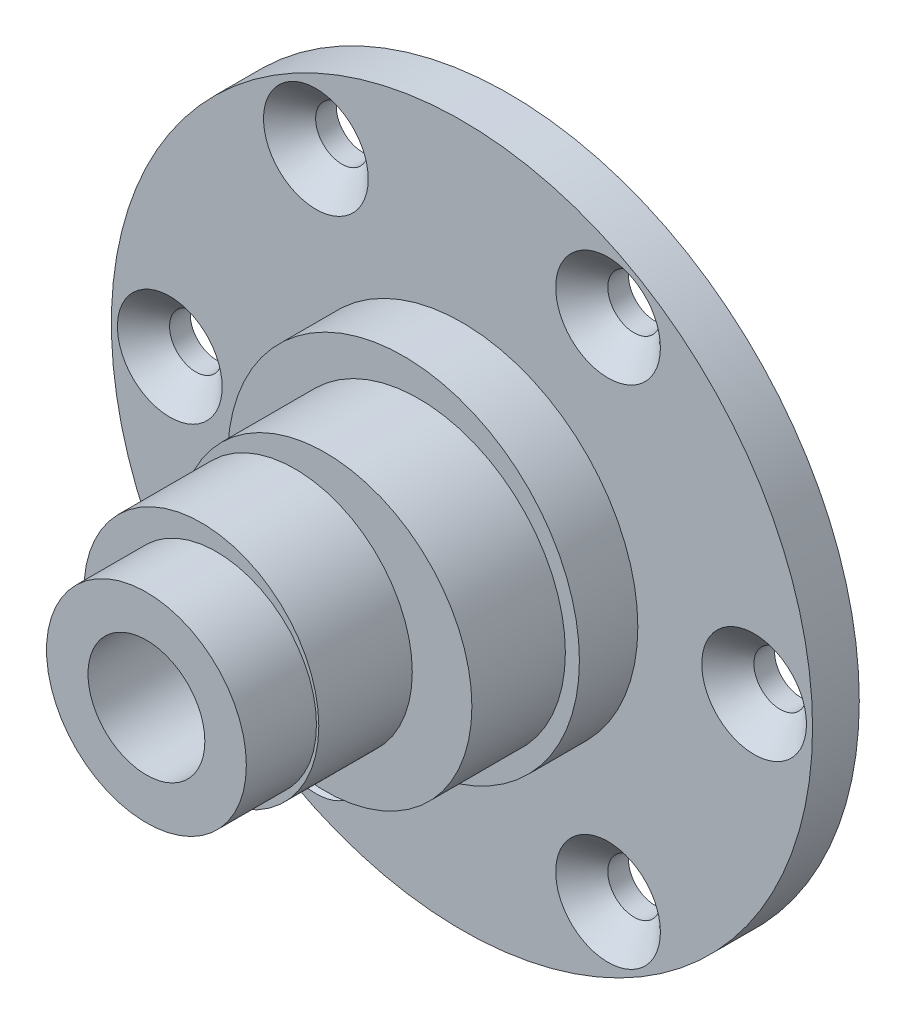
SolidWorks part; units mm, degrees
material "7075-T6, Plate (SS)"
ref_plane "Front Plane" through (0, 0, 0) normal (0, 0, 1) x (1, 0, 0)
ref_plane "Top Plane" through (0, 0, 0) normal (0, 1, 0) x (1, 0, 0)
ref_plane "Right Plane" through (0, 0, 0) normal (1, 0, 0) x (0, 0, -1)
sketch "Sketch1" plane through (0, 0, 0) normal (0, 0, 1) x (1, 0, 0)
  circle A0 centre (0, 0) radius 30 construction
  circle A1 centre (0, 0) radius 30
extrude "Boss-Extrude1" add sketch "Sketch1" along normal blind 4
sketch "Sketch2" plane through (0, 0, 4) normal (0, 0, 1) x (1, 0, 0)
  line L0 (0, 0) -> (0, 25) construction
  line L1 (0, 0) -> (-12.5, 21.6506) construction
  circle A0 centre (0, 0) radius 25 construction
  arc A3 (-44.5, 0) -> (44.5, 0) centre (0, 0) ccw
  arc A4 (44.5, 0) -> (-44.5, 0) centre (0, 0) ccw
  arc A5 (-44.5, 0) -> (44.5, 0) centre (0, 0) ccw
  arc A6 (44.5, 0) -> (-44.5, 0) centre (0, 0) ccw
  circle A11 centre (0, 0) radius 15.05
  circle A12 centre (0, 0) radius 10.05
  point P10 (-12.5, 21.6506)
  point P12 (12.5, 21.6506)
  point P13 (25, 0)
  point P14 (12.5, -21.6506)
  point P15 (-12.5, -21.6506)
  point P16 (-25, 0)
  point P17 (0, 0)
  point P22 (0, 0)
  dimension "D1" = 50
  dimension "D4" = 6
  dimension "D5" = 30.1
  dimension "D3" = 30
  dimension "D2" = 0
  dimension "D6" = 5
hole_wizard "CSK for M4 Hex Socket Countersunk Cap Screw1" positions "Sketch4" profile "Sketch3" countersink size "M4" standard "ISO" end condition through all
sketch "Sketch4" plane through (0, 0, 4) normal (0, 0, 1) x (1, 0, 0)
  point P4 (-12.5, 21.6506)
  point P7 (12.5, 21.6506)
  point P10 (25, 0)
  point P13 (-12.5, -21.6506)
  point P16 (12.5, -21.6506)
  point P19 (-25, 0)
sketch "Sketch3" plane through (-12.5, 21.6506, 4) normal (1, 0, 0) x (0, -1, 0)
  line L0 (0, 0) -> (0, 4)
  line L1 (0, 4) -> (2.25, 4)
  line L2 (2.25, 4) -> (2.25, 2.23)
  line L3 (2.25, 2.23) -> (4.48, 0)
  line L5 (4.48, 0) -> (0, 0)
  line L6 (-2.25, 2.23) -> (-4.48, 0) construction
  line L11 (0, -6.35) -> (0, 107.95) construction
  dimension "Thru Hole Dia." = 4.5
  dimension "Thru Hole Depth" = 4
  dimension "Near C'Sink Dia." = 8.96
  dimension "Near C'Sink Angle" = 90
extrude "Boss-Extrude3" add sketch "Sketch2" along normal blind 5 contours A11 A12 region at (-14.6243, 0, 4)
sketch "Sketch5" plane through (0, 0, 0) normal (0, 0, -1) x (-1, 0, 0)
  circle A0 centre (0, 0) radius 12
  dimension "D1" = 24
extrude "Cut-Extrude2" cut sketch "Sketch5" against normal blind 4
sketch "Sketch6" plane through (0, 0, 9) normal (0, 0, 1) x (1, 0, 0)
  circle A0 centre (1.3, 0) radius 12.55
  dimension "D1" = 25.1
  dimension "D2" = 1.3
extrude "Boss-Extrude4" add sketch "Sketch6" along normal blind 8
sketch "Sketch7" plane through (0, 0, 17) normal (0, 0, 1) x (1, 0, 0)
  circle A0 centre (-1.3, 0) radius 10.05
  dimension "D1" = 20.1
  dimension "D2" = 1.3
extrude "Boss-Extrude5" add sketch "Sketch7" along normal blind 8
sketch "Sketch8" plane through (0, 0, 25) normal (0, 0, 1) x (1, 0, 0)
  circle A0 centre (0, 0) radius 8.55
  dimension "D1" = 17.1
extrude "Boss-Extrude6" add sketch "Sketch8" along normal blind 6
sketch "Sketch9" plane through (0, 0, 31) normal (0, 0, 1) x (1, 0, 0)
  circle A0 centre (0, 0) radius 5
  dimension "D1" = 10
extrude "Cut-Extrude3" cut sketch "Sketch9" against normal blind 30
